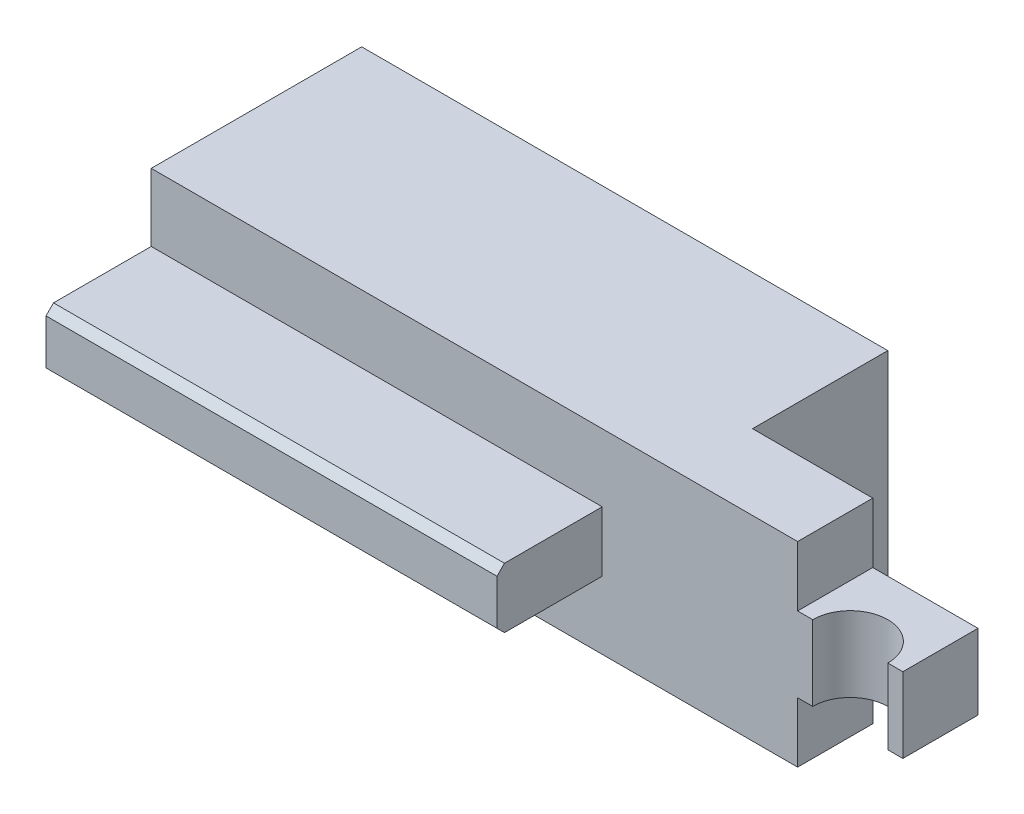
SolidWorks part; units mm, degrees
ref_plane "前视基准面" through (0, 0, 0) normal (0, 0, 1) x (1, 0, 0)
ref_plane "上视基准面" through (0, 0, 0) normal (0, 1, 0) x (1, 0, 0)
ref_plane "右视基准面" through (0, 0, 0) normal (1, 0, 0) x (0, 0, -1)
sketch "草图1" plane through (0, 0, 0) normal (1, 0, 0) x (0, 0, -1)
  line L0 (-15.5739, 0) -> (17.5206, 0) construction
  line L1 (0, 0) -> (0, 24.6123) construction
  line L2 (0, 0) -> (25, 0)
  line L3 (25, 0) -> (25, 17)
  line L4 (25, 17) -> (0, 17)
  line L5 (0, 17) -> (0, 0)
extrude "凸台-拉伸1" add sketch "草图1" along normal blind 50
sketch "草图2" plane through (0, 0, 0) normal (-1, 0, 0) x (0, 0, 1)
  line L0 (0, 17) -> (0, 11)
  line L1 (0, 17) -> (0, 0) construction
  line L2 (0, 11) -> (-11, 11)
  line L3 (-11, 11) -> (-11, 17)
  line L4 (-25, 17) -> (0, 17) construction
  line L5 (-11, 17) -> (0, 17)
  line L6 (-25, 8.5) -> (0, 8.5) construction
  line L7 (-25, 0) -> (-25, 17) construction
  line L8 (-11, 6) -> (-11, 0)
  line L9 (0, 6) -> (-11, 6)
  line L10 (0, 0) -> (0, 6)
  line L11 (-11, 0) -> (0, 0)
extrude "切除-拉伸1" cut sketch "草图2" against normal blind 50 contours L5 L0 L2 L3 | L8 L11 L10 L9
sketch "草图3" plane through (0, 11, 0) normal (0, 1, 0) x (1, 0, 0)
  line L0 (50, 0) -> (50, 11)
  line L1 (50, 11) -> (30, 11)
  line L2 (50, 11) -> (0, 11) construction
  line L3 (30, 11) -> (30, 0)
  line L4 (50, 0) -> (0, 0) construction
  line L5 (30, 0) -> (50, 0)
extrude "切除-拉伸2" cut sketch "草图3" against normal blind 50
sketch "草图4" plane through (0, 0, -25) normal (0, 0, -1) x (-1, 0, 0)
  line L0 (-50, 8.5) -> (0, 8.5) construction
  line L1 (-50, 0) -> (-50, 17) construction
  line L2 (0, 0) -> (0, 17) construction
  line L4 (-50, 11) -> (-43, 11)
  line L5 (-43, 11) -> (-43, 17)
  line L6 (-50, 17) -> (0, 17) construction
  line L7 (-43, 17) -> (-50, 17)
  line L8 (-50, 17) -> (-50, 11)
  line L9 (-50, 0) -> (-50, 6)
  line L10 (-43, 0) -> (-50, 0)
  line L11 (-43, 6) -> (-43, 0)
  line L12 (-50, 6) -> (-43, 6)
extrude "切除-拉伸3" cut sketch "草图4" against normal blind 50
sketch "草图5" plane through (0, 11, 0) normal (0, 1, 0) x (1, 0, 0)
  line L1 (50, 11) -> (50, 25) construction
  line L2 (50, 16) -> (43, 16)
  line L3 (43, 11) -> (43, 25) construction
  line L4 (43, 16) -> (43, 25)
  line L5 (43, 25) -> (50, 25)
  line L6 (50, 25) -> (50, 16)
extrude "切除-拉伸4" cut sketch "草图5" against normal blind 50 contours L2 L4 L5 L6
sketch "草图6" plane through (0, 11, 0) normal (0, 1, 0) x (1, 0, 0)
  line L0 (43, 11) -> (50, 11) construction
  circle A0 centre (46.5, 11) radius 2.5
extrude "切除-拉伸5" cut sketch "草图6" against normal blind 50
sketch "草图7" plane through (0, 0, 0) normal (-1, 0, 0) x (0, 0, 1)
  line L0 (0, 8.5) -> (-25, 8.5)
  line L1 (0, 11) -> (0, 6) construction
  line L2 (-25, 0) -> (-25, 17) construction
  line L3 (-25, 17) -> (-25, 15)
  line L4 (-25, 15) -> (-11, 15)
  line L5 (-11, 11) -> (-11, 17) construction
  line L6 (-11, 15) -> (-11, 17)
  line L7 (-11, 17) -> (-25, 17)
  line L8 (-11, 2) -> (-11, 0)
  line L9 (-25, 2) -> (-11, 2)
  line L10 (-25, 0) -> (-25, 2)
  line L11 (-11, 0) -> (-25, 0)
  line M6 (-11, 11) -> (-11, 17)
  line M7 (-11, 17) -> (-25, 17)
  line M8 (-25, 17) -> (-25, 0)
  line M9 (-25, 0) -> (-11, 0)
  line M10 (-11, 0) -> (-11, 6)
extrude "切除-拉伸8" cut sketch "草图7" against normal blind 50 contours L4 M8 M6 M7 | L9 M8 M9 M10 region at (0, 16, -18) region at (0, 1, -18)
sketch "草图10" plane through (0, 0, 0) normal (-1, 0, 0) x (0, 0, 1)
  line L0 (0, 11) -> (-4, 11)
  line L1 (0, 11) -> (-11, 11) construction
  line L2 (-4, 11) -> (-4, 6)
  line L3 (0, 6) -> (-11, 6) construction
  line L4 (-4, 6) -> (0, 6)
  line L5 (0, 6) -> (0, 11)
extrude "切除-拉伸9" cut sketch "草图10" against normal blind 50
sketch "草图11" plane through (0, 0, 0) normal (-1, 0, 0) x (0, 0, 1)
  line L0 (-22, 12) -> (-22, 5)
  line L3 (-22, 12) -> (-14, 12)
  line L4 (-14, 12) -> (-14, 5)
  line L5 (-14, 5) -> (-22, 5)
extrude "切除-拉伸10" cut sketch "草图11" against normal blind 30
sketch "草图12" plane through (0, 0, 0) normal (-1, 0, 0) x (0, 0, 1)
  line L0 (-4, 8.5) -> (-25, 8.5) construction
  line L1 (-4, 11) -> (-4, 6) construction
  line L2 (-25, 2) -> (-25, 15) construction
  line L3 (-4, 11) -> (-4, 10)
  line L4 (-4, 11) -> (-5, 11)
  line L5 (-4, 11) -> (-11, 11) construction
  line L6 (-5, 11) -> (-4, 10)
  line L7 (-4, 6) -> (-5, 6)
  line L8 (-4, 6) -> (-4, 7)
  line L9 (-5, 6) -> (-4, 7)
extrude "切除-拉伸11" cut sketch "草图12" against normal blind 50 contours L6 L3 L4 | L7 L9 L8
sketch "草图13" plane through (0, 0, 0) normal (-1, 0, 0) x (0, 0, 1)
  line L0 (-11, 11) -> (-11, 10.5)
  line L1 (-11, 10.5) -> (-4.5, 10.5)
  line L2 (-5, 11) -> (-4, 10) construction
  line L3 (-4.5, 10.5) -> (-5, 11)
  line L4 (-5, 11) -> (-11, 11)
  line L5 (-4, 8.5) -> (-25, 8.5) construction
  line L6 (-4, 10) -> (-4, 7) construction
  line L7 (-25, 2) -> (-25, 15) construction
  line L8 (-4.5, 6.5) -> (-5, 6)
  line L9 (-11, 6.5) -> (-4.5, 6.5)
  line L10 (-11, 6) -> (-11, 6.5)
  line L11 (-5, 6) -> (-11, 6)
extrude "切除-拉伸12" cut sketch "草图13" against normal blind 50
sketch "草图14" plane through (0, 0, -25) normal (0, 0, -1) x (-1, 0, 0)
  circle A0 centre (-3, 8.5) radius 1.55
  circle A1 centre (-11, 8.5) radius 1.55
extrude "切除-拉伸13" cut sketch "草图14" against normal blind 5 contours A0 | A1 | A1 region at (3, 8.5, -25) region at (11, 8.5, -25)
sketch "Skizze1" plane through (43, 0, 0) normal (1, 0, 0) x (0, 0, -1)
  line L1 (25, 15) -> (11, 15) construction
  line L5 (25, 2) -> (11, 2) construction
  line L7 (16, 15) -> (16, 2)
  line L9 (16, 15) -> (25, 15)
  line L10 (25, 15) -> (25, 2)
  line L11 (25, 2) -> (16, 2)
extrude "Schnitt-Linear austragen1" cut sketch "Skizze1" against normal blind 8
